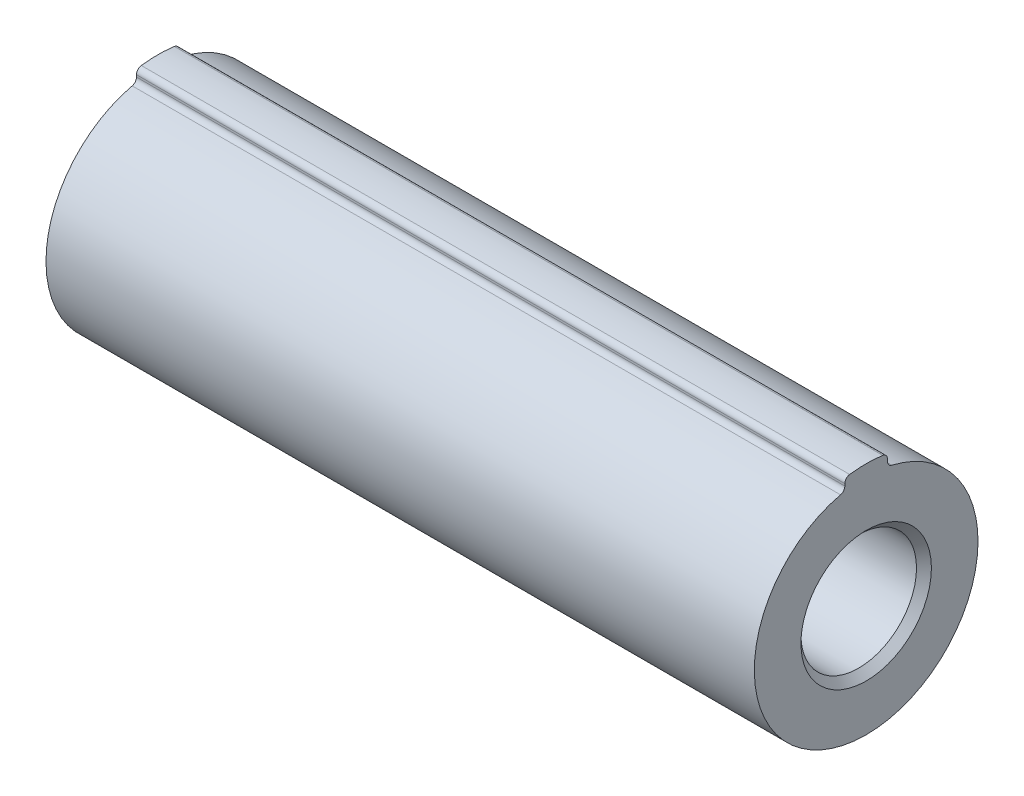
SolidWorks part; units mm, degrees
ref_plane "前视基准面" through (0, 0, 0) normal (0, 0, 1) x (1, 0, 0)
ref_plane "上视基准面" through (0, 0, 0) normal (0, 1, 0) x (1, 0, 0)
ref_plane "右视基准面" through (0, 0, 0) normal (1, 0, 0) x (0, 0, -1)
other "Configuration Table"
sketch "草图1" plane through (0, 0, 0) normal (1, 0, 0) x (0, 0, -1)
  circle A0 centre (0, 0) radius 6
  dimension "D1" = 12
extrude "凸台-拉伸1" add sketch "草图1" along normal blind 18 and the other way blind 20
sketch "草图3" plane through (18, 0, 0) normal (1, 0, 0) x (0, 0, -1)
  circle A0 centre (0, 0) radius 3.1
  dimension "D1" = 6.2
extrude "切除-拉伸1" cut sketch "草图3" against normal blind 16
sketch "草图4" plane through (-20, 0, 0) normal (-1, 0, 0) x (0, 0, 1)
  circle A0 centre (0, 0) radius 4.1
  dimension "D1" = 8.2
extrude "切除-拉伸2" cut sketch "草图4" against normal blind 20
sketch "草图5" plane through (2, 0, 0) normal (1, 0, 0) x (0, 0, -1)
  line L0 (-1.6882, 2.6) -> (1.6882, 2.6)
  circle A0 centre (0, 0) radius 3.1 construction
  arc A1 (1.6882, 2.6) -> (-1.6882, 2.6) centre (0, 0) ccw
  arc A2 (-1.6882, 2.6) -> (1.6882, 2.6) centre (0, 0) ccw construction
  dimension "D1" = 2.6
extrude "凸台-拉伸2" add sketch "草图5" along normal blind 12
sketch "草图6" plane through (0, 0, 0) normal (-1, 0, 0) x (0, 0, 1)
  line L0 (-1.7482, 3.7086) -> (2.1694, 3.4791)
  circle A0 centre (0, 0) radius 4.1 construction
  arc A1 (2.1694, 3.4791) -> (-1.7482, 3.7086) centre (0, 0) ccw
  arc A2 (-1.7482, 3.7086) -> (2.1694, 3.4791) centre (0, 0) ccw construction
  dimension "D1" = 3.6
extrude "凸台-拉伸3" add sketch "草图6" along normal blind 15
chamfer "倒角1" distance 0.4 angle 45 2 edges at (18, 0, -3.1) (-20, 0, 4.1)
chamfer "倒角2" distance 0.5 angle 45 2 edges at (-15, 3.5938, 0.2106) (14, 2.6, 0)
sketch "草图7" plane through (18, 0, 0) normal (1, 0, 0) x (0, 0, -1)
  line L0 (-1.1446, 6.5) -> (1.1446, 6.5) construction
  line L1 (-1.1446, 6.5) -> (-1.1446, 4)
  line L2 (1.1446, 6.5) -> (1.1446, 4)
  line L3 (-1.1446, 4) -> (1.1446, 4)
  arc A1 (-1.1446, 6.5) -> (1.1446, 6.5) centre (0, 0) ccw construction
  circle A2 centre (0, 0) radius 6.6
  arc A3 (1.1446, 6.5) -> (-1.1446, 6.5) centre (0, 0) ccw
  dimension "D2" = 4
  dimension "D3" = 6.5
  dimension "D1" = 0.6
extrude "凸台-拉伸4" add sketch "草图7" against normal up to surface (38 mm away) up to face at (-20, 0, -4.5)
fillet "圆角1" radius 0.3 4 edges at (-1, 6.5, -1.1446) (-1, 5.8898, -1.1446) (-1, 6.5, 1.1446) (-1, 5.8898, 1.1446)
